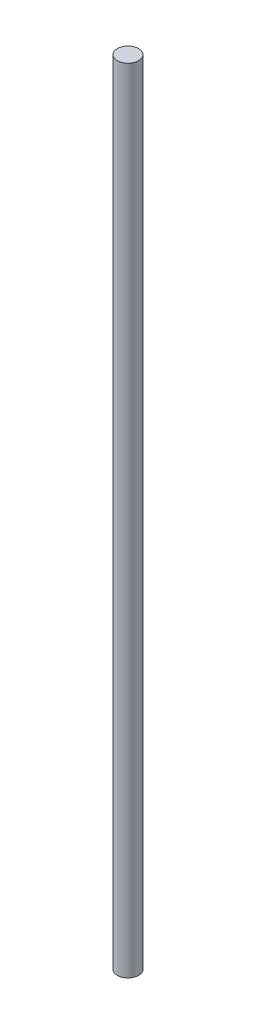
SolidWorks part; units mm, degrees
ref_plane "Front Plane" through (0, 0, 0) normal (0, 0, 1) x (1, 0, 0)
ref_plane "Top Plane" through (0, 0, 0) normal (0, 1, 0) x (1, 0, 0)
ref_plane "Right Plane" through (0, 0, 0) normal (1, 0, 0) x (0, 0, -1)
sketch "Sketch1" plane through (0, 0, 0) normal (0, 1, 0) x (1, 0, 0)
  circle A0 centre (0, 0) radius 3.175
  dimension "D1" = 6.35
extrude "Boss-Extrude1" add sketch "Sketch1" along normal blind 237.3
